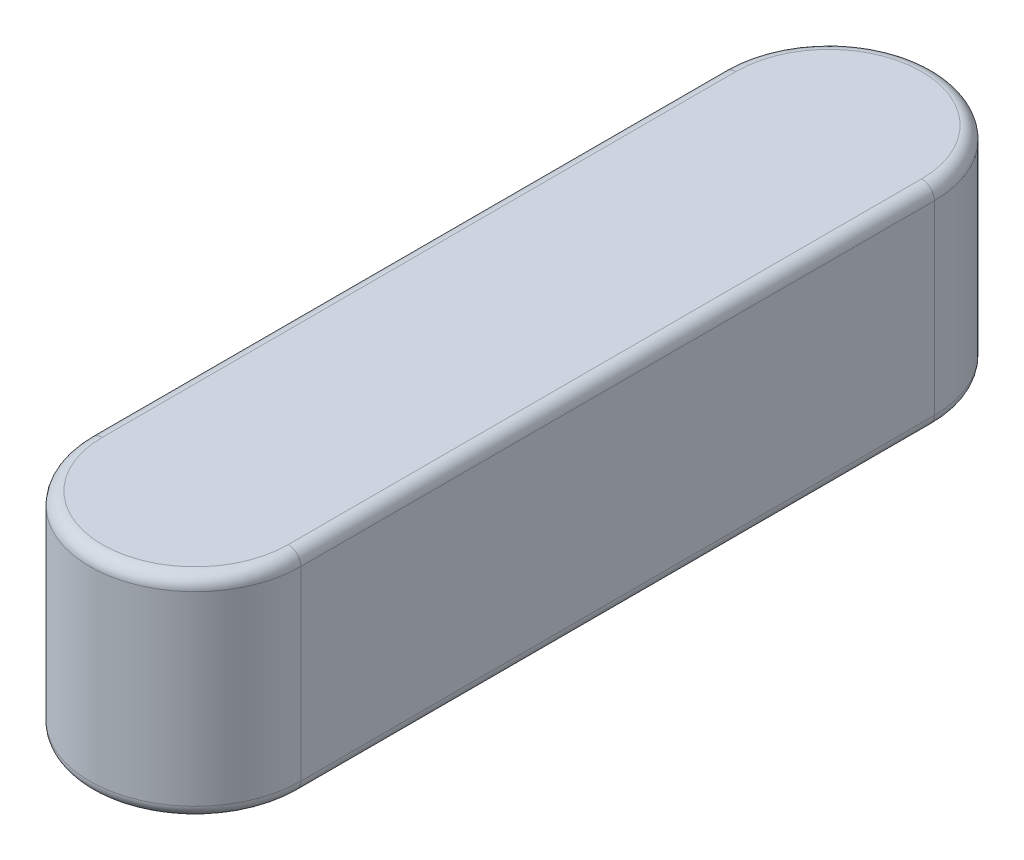
SolidWorks part; units mm, degrees
material "Plain Carbon Steel"
ref_plane "Front Plane" through (0, 0, 0) normal (0, 0, 1) x (1, 0, 0)
ref_plane "Top Plane" through (0, 0, 0) normal (0, 1, 0) x (1, 0, 0)
ref_plane "Right Plane" through (0, 0, 0) normal (1, 0, 0) x (0, 0, -1)
sketch "Sketch1" plane through (0, 0, 0) normal (0, 0, 1) x (1, 0, 0)
  line L1 (-2.5, -2.5) -> (2.5, -2.5)
  line L2 (-2.5, -2.5) -> (-2.5, 2.5)
  line L3 (-2.5, 2.5) -> (2.5, 2.5)
  line L4 (2.5, -2.5) -> (2.5, 2.5)
  line L5 (-2.5, -2.5) -> (2.5, 2.5) construction
  line L6 (-2.5, 2.5) -> (2.5, -2.5) construction
  point P0 (0, 0)
  dimension "D1" = 5
  dimension "D2" = 5
extrude "Boss-Extrude1" add sketch "Sketch1" along normal mid plane 20
fillet "Fillet1" 2 edges at (2.5, 0, 10) (-2.5, 0, 10) type full round first side face at (2.5, 0, 0) second side face at (-2.5, 0, 0) middle face at (0, 0, 10)
fillet "Fillet2" 2 edges at (2.5, 0, -10) (-2.5, 0, -10) type full round first side face at (2.5, 0, -1.25) second side face at (-2.5, 0, -1.25) middle face at (0, 0, -10)
fillet "Fillet3" radius 0.3 8 edges at (0, -2.5, 10) (2.5, -2.5, 0) (0, -2.5, -10) (-2.5, -2.5, 0) (0, 2.5, 10) (-2.5, 2.5, 0) (0, 2.5, -10) (2.5, 2.5, 0)
